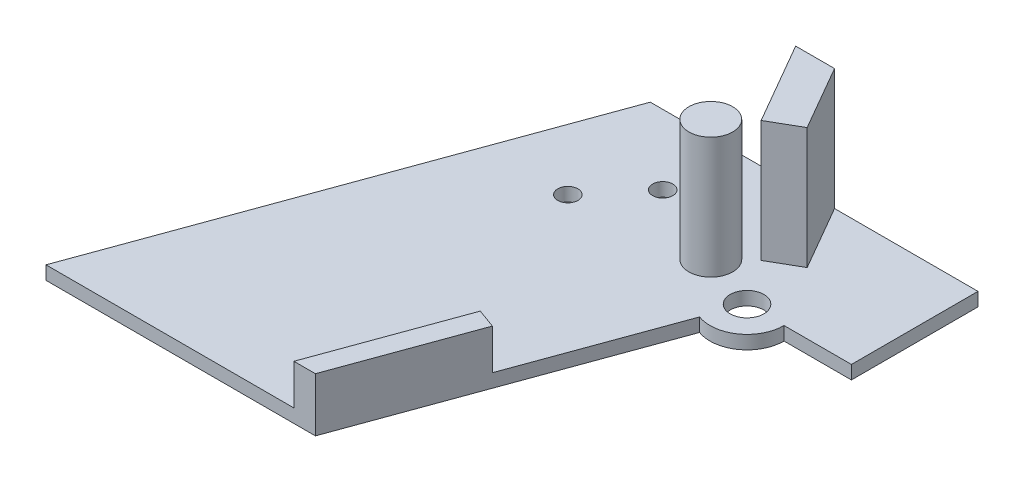
SolidWorks part; units mm, degrees
ref_plane "Front Plane" through (0, 0, 0) normal (0, 0, 1) x (1, 0, 0)
ref_plane "Top Plane" through (0, 0, 0) normal (0, 1, 0) x (1, 0, 0)
ref_plane "Right Plane" through (0, 0, 0) normal (1, 0, 0) x (0, 0, -1)
sketch "Sketch1" plane through (0, 0, 0) normal (0, 1, 0) x (1, 0, 0)
  line L0 (0, 0) -> (23.9414, 65.7785)
  line L1 (23.9414, 65.7785) -> (72.601, 65.7785)
  line L2 (72.601, 65.7785) -> (72.601, 46.9846)
  line L3 (72.601, 46.9846) -> (62.601, 46.9846)
  line L5 (40, 0) -> (0, 0)
  line L6 (36.8075, 0) -> (44.1923, 20.2898)
  line L7 (44.1923, 20.2898) -> (47.0114, 19.2637)
  line L8 (47.0114, 19.2637) -> (55.2199, 41.8163)
  line L10 (55.2199, 41.8163) -> (57.101, 46.9846) construction
  line L11 (57.101, 46.9846) -> (62.601, 46.9846) construction
  line L12 (47.0114, 19.2637) -> (40, 0)
  line L13 (57.101, 46.9846) -> (48.6438, 50.0628) construction
  line L14 (40, 0) -> (37.1809, 1.0261) construction
  line L15 (52.5285, 53.6541) -> (19.5285, 53.6541) construction
  line L16 (48.6438, 50.0628) -> (31.6438, 50.0628) construction
  line L17 (36.1433, 55.4251) -> (29.7154, 47.7647) construction
  line L18 (45.5285, 65.7785) -> (52.5285, 53.6541)
  line L19 (52.5285, 53.6541) -> (56.8586, 56.1541)
  line L20 (56.8586, 56.1541) -> (51.302, 65.7785)
  circle A0 centre (57.101, 46.9846) radius 2.5
  arc A1 (55.2199, 41.8163) -> (62.601, 46.9846) centre (57.101, 46.9846) ccw
  circle A2 centre (48.6438, 50.0628) radius 3.25
  circle A3 centre (29.7154, 47.7647) radius 1.5
  circle A4 centre (36.1433, 55.4251) radius 1.5
  dimension "D6" = 5
  dimension "D14" = 6.5
  dimension "D15" = 3
  dimension "D16" = 3
  dimension "D1" = 40
  dimension "D2" = 50
  dimension "D4" = 70
  dimension "D7" = 3
  dimension "D9" = 3
  dimension "D8" = 18.7939
  dimension "D5" = 24
  dimension "D13" = 9
  dimension "D12" = 110
  dimension "D10" = 10
  dimension "D3" = 17
  dimension "D11" = 10
  dimension "D17" = 5
  dimension "D18" = 14
  dimension "D19" = 130
  dimension "D20" = 120
  dimension "D21" = 33
  dimension "D22" = 7
extrude "Boss-Extrude1" add sketch "Sketch1" along normal blind 20 contours A2 | L19 L20 L1 L18 region at (51.4576, 0, -60.3174) region at (48.6438, 0, -50.0628)
extrude "Boss-Extrude3" add sketch "Sketch1<5>" along normal blind 8 separate body contours L12 L7 L6 L5 region at (41.9898, 0, -9.8906)
sketch "Sketch1<5>" plane through (0, 0, 0) normal (0, 1, 0) x (1, 0, 0) same geometry as "Sketch1"
extrude "Boss-Extrude4" add sketch "Sketch1<6>" along normal blind 2 contours L8 A1 L3 L2 L1 L20 L19 L18 L0 L5 L6 L7 A4 A3 A2 A0 region at (34.0795, 0, -34.4057)
sketch "Sketch1<6>" plane through (0, 0, 0) normal (0, 1, 0) x (1, 0, 0) same geometry as "Sketch1"
equation "\"D16@Sketch1\"=\"D15@Sketch1\""
